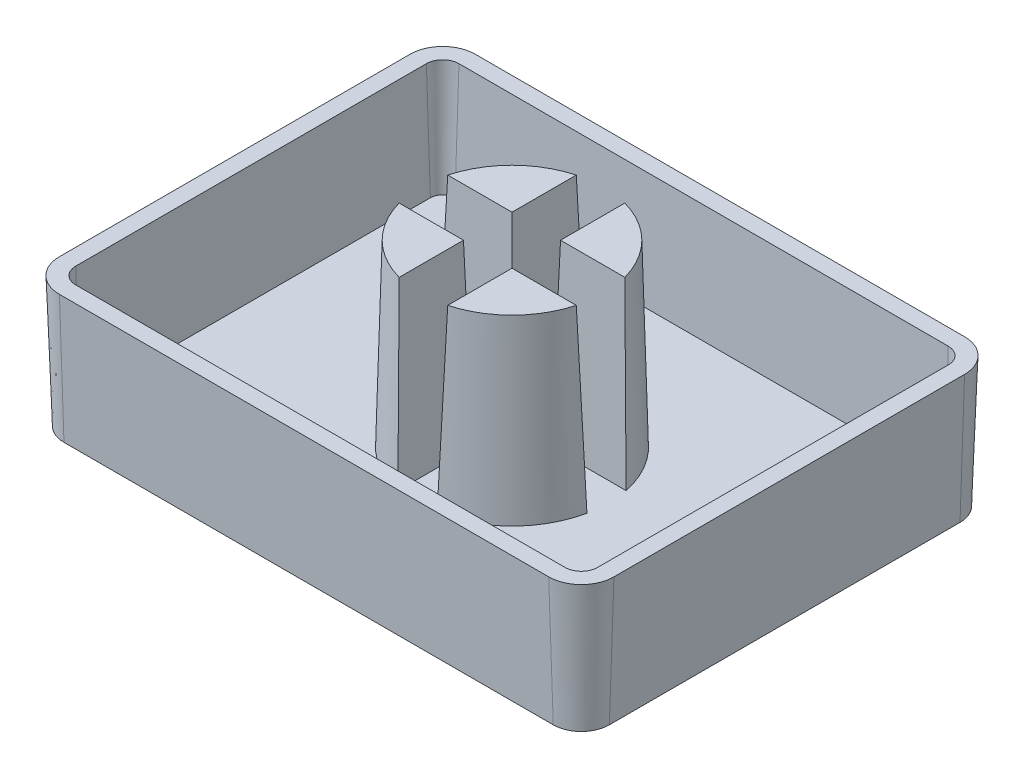
SolidWorks part; units mm, degrees
ref_plane "Front Plane" through (0, 0, 0) normal (0, 0, 1) x (1, 0, 0)
ref_plane "Top Plane" through (0, 0, 0) normal (0, 1, 0) x (1, 0, 0)
ref_plane "Right Plane" through (0, 0, 0) normal (1, 0, 0) x (0, 0, -1)
sketch "Sketch1" plane through (0, 0, 0) normal (0, 1, 0) x (1, 0, 0)
  line L1 (-7.5, -6.375) -> (7.5, -6.375)
  line L2 (-8.5, -5.375) -> (-8.5, 5.375)
  line L3 (-7.5, 6.375) -> (7.5, 6.375)
  line L4 (8.5, -5.375) -> (8.5, 5.375)
  line L5 (-8.5, -6.375) -> (8.5, 6.375) construction
  line L6 (-8.5, 6.375) -> (8.5, -6.375) construction
  arc A0 (-8.5, 5.375) -> (-7.5, 6.375) centre (-7.5, 5.375) cw
  arc A1 (8.5, 5.375) -> (7.5, 6.375) centre (7.5, 5.375) ccw
  arc A2 (8.5, -5.375) -> (7.5, -6.375) centre (7.5, -5.375) cw
  arc A3 (-7.5, -6.375) -> (-8.5, -5.375) centre (-7.5, -5.375) cw
  point P0 (0, 0)
  dimension "D3" = 1
  dimension "D1" = 17
  dimension "D2" = 12.75
extrude "Boss-Extrude1" add sketch "Sketch1" against normal blind 4 draft 2
shell "Shell1" thickness 0.5 removed face at (0, 0, 0)
sketch "Sketch3" plane through (0, -3.5, 0) normal (0, 1, 0) x (1, 0, 0)
  line L0 (-0.6, 2.8977) -> (-0.6, 0.6)
  line L1 (-2.8977, 0.6) -> (-0.6, 0.6)
  line L2 (0, -2.2) -> (0, 2.2) construction
  line L3 (-2.2, 0) -> (2.2, 0) construction
  line L4 (0.6, 2.8977) -> (0.6, 0.6)
  line L5 (-2.8977, -0.6) -> (-0.6, -0.6)
  line L6 (-0.6, -0.6) -> (-0.6, -2.8977)
  line L7 (0.6, -0.6) -> (0.6, -2.8977)
  line L8 (0.6, -0.6) -> (2.8977, -0.6)
  line L9 (0.6, 0.6) -> (2.8977, 0.6)
  arc A0 (-2.8977, -0.6) -> (-0.6, -2.8977) centre (0, 0) ccw
  arc A1 (2.8977, 0.6) -> (0.6, 2.8977) centre (0, 0) ccw
  arc A2 (0.6, -2.8977) -> (2.8977, -0.6) centre (0, 0) ccw
  arc A3 (-0.6, 2.8977) -> (-2.8977, 0.6) centre (0, 0) ccw
  dimension "D1" = 0.6
  dimension "D2" = 0.6
extrude "Boss-Extrude2" add sketch "Sketch3" along normal blind 5.5 draft 1.5
